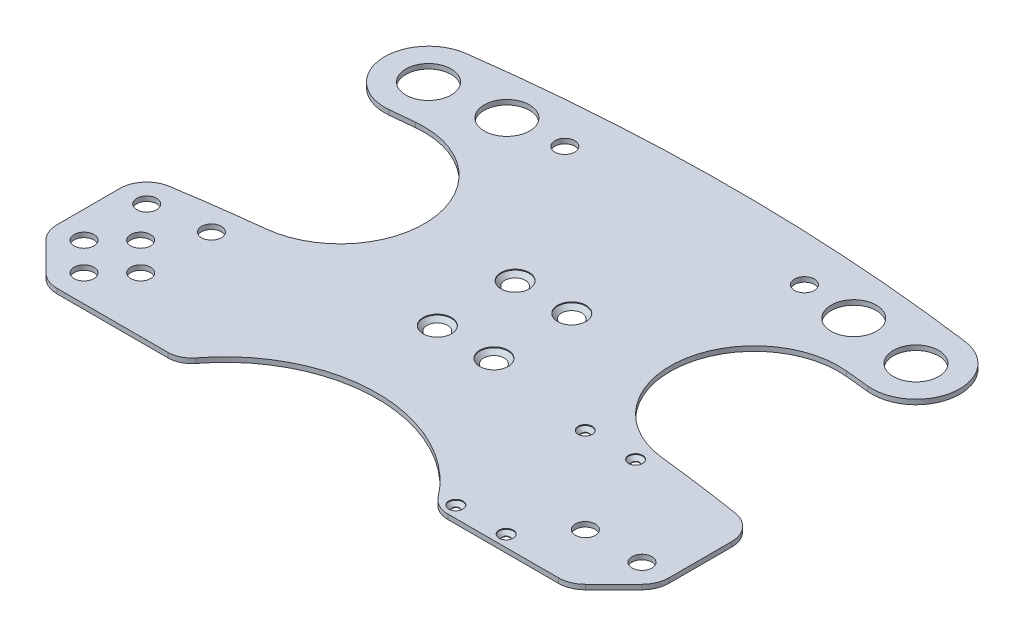
SolidWorks part; units mm, degrees
ref_plane "Front Plane" through (0, 0, 0) normal (0, 0, 1) x (1, 0, 0)
ref_plane "Top Plane" through (0, 0, 0) normal (0, 1, 0) x (1, 0, 0)
ref_plane "Right Plane" through (0, 0, 0) normal (1, 0, 0) x (0, 0, -1)
sketch "Sketch1" plane through (0, 0, 0) normal (0, 1, 0) x (1, 0, 0)
  line L1 (-120, -95) -> (120, -95)
  line L2 (-120, -95) -> (-120, 95)
  line L3 (-120, 95) -> (120, 95)
  line L4 (120, -95) -> (120, 95)
  line L5 (-120, -95) -> (120, 95) construction
  line L6 (-120, 95) -> (120, -95) construction
  line L7 (-10, 13.75) -> (10, 13.75)
  line L8 (-10, 13.75) -> (-10, -13.75)
  line L9 (-10, -13.75) -> (10, -13.75)
  line L10 (10, 13.75) -> (10, -13.75)
  line L11 (-10, 13.75) -> (10, -13.75) construction
  line L12 (-10, -13.75) -> (10, 13.75) construction
  circle A0 centre (0, 0) radius 95
  circle A1 centre (-10, 13.75) radius 2.5
  circle A2 centre (10, 13.75) radius 2.5
  circle A3 centre (10, -13.75) radius 2.5
  circle A4 centre (-10, -13.75) radius 2.5
  circle A5 centre (0, 0) radius 120
  dimension "D3" = 5
  dimension "D1" = 240
  dimension "D2" = 190
  dimension "D4" = 27.5
  dimension "D5" = 20
extrude "Boss-Extrude1" add sketch "Sketch1" along normal blind 1.7 contours A0 A4 L8 A1 L7 A2 L10 A3 L9 | A4 L9 A3 L10 A2 L7 A1 L8 | L3 A5 L1 A0 | L1 A5 L3 A0 region at (-105.6812, 0, 51.9346) region at (68.7642, 0, 68.7642) region at (-92.313, 0, 0) region at (0, 0, 0)
sketch "Sketch2" plane through (0, 1.7, 0) normal (0, 1, 0) x (1, 0, 0)
  line L0 (-81.1673, -40) -> (21.9115, -40) construction
  line L1 (-127.3056, -60) -> (138.909, -60) construction
  line L2 (-88.5406, 28.139) -> (-88.5406, -89.0376) construction
  line L3 (-88.5406, -40) -> (-88.5406, -60) construction
  line L4 (0, 21.6044) -> (0, -21.4213) construction
  line L5 (88.5406, 33.139) -> (88.5406, -84.0376) construction
  line L6 (-151.9803, -25) -> (55.006, -25) construction
  line L7 (-48.8837, 35) -> (62.426, 35) construction
  circle A0 centre (0, 0) radius 35
  circle A1 centre (0, 35) radius 2.5
  circle A2 centre (30.3109, 17.5) radius 2.5
  circle A3 centre (30.3109, -17.5) radius 2.5
  circle A4 centre (0, -35) radius 2.5
  circle A5 centre (-30.3109, -17.5) radius 2.5
  circle A6 centre (-30.3109, 17.5) radius 2.5
  circle A7 centre (-88.5406, -40) radius 3.5
  circle A8 centre (-88.5406, -50) radius 10
  circle A9 centre (-78.5406, -50) radius 3.5
  circle A10 centre (-88.5406, -60) radius 3.5
  circle A11 centre (-98.5406, -50) radius 3.5
  circle A12 centre (78.5406, -50) radius 3.5
  circle A13 centre (98.5406, -50) radius 3.5
  circle A14 centre (-98.5406, -27.8625) radius 3.5
  circle A15 centre (-78.5406, -25) radius 3.5
  circle A16 centre (0, 0) radius 45
  circle A17 centre (0, -580) radius 625
  circle A18 centre (0, -580) radius 645
  circle A19 centre (-86.0945, 59.2282) radius 8
  circle A20 centre (-61.2596, 62.0843) radius 8
  circle A21 centre (-86.0945, 59.2282) radius 15.5
  arc A22 (-73.3144, 95) -> (-73.3144, -95) centre (0, 0) ccw construction
  circle A23 centre (-61.2596, 62.0843) radius 9.5
  circle A24 centre (-86.0945, 59.2282) radius 9.5
  circle A25 centre (61.2596, 62.0843) radius 8
  circle A26 centre (86.0945, 59.2282) radius 8
  circle A27 centre (-42.3209, 63.6101) radius 3.5
  circle A28 centre (0, 0) radius 70
  circle A29 centre (42.3209, 63.6101) radius 3.5
  circle A30 centre (-98.5406, -50) radius 9.5
  circle A31 centre (42.3209, 63.6101) radius 9.5
  circle A32 centre (61.2596, 62.0843) radius 9.5
  circle A33 centre (0, -645.0455) radius 625
  point P17 (0, 0)
  point P21 (-88.5406, -50)
  point P37 (-88.5406, -50)
  point P56 (0, 65)
  point P57 (0, 45)
  point P68 (-76.6704, 60.4269)
  point P69 (-70.7097, 61.1124)
  dimension "D1" = 70
  dimension "D2" = 5
  dimension "D4" = 7
  dimension "D9" = 90
  dimension "D10" = 1250
  dimension "D11" = 20
  dimension "D12" = 16
  dimension "D14" = 6
  dimension "D13" = 19
  dimension "D17" = 140
  dimension "D18" = 6
  dimension "D5" = 20
  dimension "D6" = 40
  dimension "D8" = 15
  dimension "D15" = 6
  dimension "D3" = 6
  dimension "D7" = 4
extrude "Cut-Extrude1" cut sketch "Sketch2" against normal up to next contours A7 | A9 | A10 | A11 | A12 | A13 | A14 | A15 | A19 | A20 | A25 | A26 | A27 | A29
sketch "Sketch3" plane through (0, 1.7, 0) normal (0, 1, 0) x (1, 0, 0)
  line L1 (-84.5506, 43.8053) -> (-40.7771, 48.1872)
  line L2 (0, 100.6986) -> (0, -98.8678) construction
  line L3 (-10.3445, 0) -> (20.4144, 0) construction
  line L5 (84.5506, 43.8053) -> (40.7771, 48.1872)
  line L6 (-42.3209, 63.6101) -> (0, 0) construction
  line L7 (-36.306, 26.5871) -> (-55.2257, 55.0243)
  line L8 (-10.4964, 43.7587) -> (-29.4161, 72.1959)
  line L9 (10.4964, 43.7587) -> (29.4161, 72.1959)
  line L10 (36.306, 26.5871) -> (55.2257, 55.0243)
  line L11 (-108.0406, -50) -> (-108.0406, -27.8625)
  line L13 (-73.3144, -95) -> (73.3144, -95)
  line L14 (73.3144, 95) -> (-73.3144, 95)
  line L15 (-73.3144, -95) -> (73.3144, -95)
  line L16 (73.3144, 95) -> (-73.3144, 95)
  line L17 (-69.0406, -25) -> (-69.0406, -50)
  line L18 (-71.8231, -56.7175) -> (-81.8231, -66.7175)
  line L19 (-105.2581, -56.7175) -> (-95.2581, -66.7175)
  line L20 (-42.3209, 79.1101) -> (42.3209, 79.1101)
  line L21 (-78.5406, -15.5) -> (-42.2463, -15.5)
  line L22 (0, -45) -> (111.243, -45) construction
  line L23 (-88.5406, -69.5) -> (88.5406, -69.5)
  line L24 (69.0406, -15.5) -> (45.0406, -15.5)
  line L25 (78.5406, -15.5) -> (42.2463, -15.5)
  line L27 (108.0406, -50) -> (108.0406, -27.8625)
  line L28 (105.2581, -56.7175) -> (95.2581, -66.7175)
  line L29 (69.0406, -15.5) -> (69.0406, -69.5)
  line L30 (69.0406, -69.5) -> (45.0406, -69.5)
  line L31 (45.0406, -15.5) -> (45.0406, -69.5)
  line L32 (57.0406, -15.5) -> (57.0406, -69.5) construction
  line L33 (45.0406, -42.5) -> (69.0406, -42.5) construction
  circle A0 centre (-86.0945, 59.2282) radius 15.5
  arc A1 (-73.3144, 95) -> (-73.3144, -95) centre (0, 0) ccw construction
  circle A2 centre (-42.3209, 63.6101) radius 15.5
  circle A3 centre (86.0945, 59.2282) radius 15.5
  circle A4 centre (42.3209, 63.6101) radius 15.5
  circle A5 centre (0, 0) radius 45
  circle A6 centre (-98.5406, -27.8625) radius 9.5
  circle A7 centre (-98.5406, -27.8625) radius 3.5 construction
  arc A8 (-73.3144, 95) -> (-73.3144, -95) centre (0, 0) ccw
  arc A9 (73.3144, -95) -> (73.3144, 95) centre (0, 0) ccw
  arc A10 (-73.3144, 95) -> (-73.3144, -95) centre (0, 0) ccw
  arc A11 (73.3144, -95) -> (73.3144, 95) centre (0, 0) ccw
  circle A12 centre (-78.5406, -25) radius 9.5
  circle A13 centre (-88.5406, -60) radius 9.5
  circle A14 centre (-98.5406, -50) radius 9.5
  circle A15 centre (-78.5406, -50) radius 9.5
  circle A17 centre (98.5406, -50) radius 9.5
  circle A18 centre (78.5406, -50) radius 9.5
  arc A19 (73.3144, -95) -> (73.3144, 95) centre (0, 0) ccw construction
  arc A20 (-45.0406, -69.5) -> (45.0406, -69.5) centre (0, -98.6511) cw
  circle A21 centre (98.5406, -27.8625) radius 9.5
  circle A22 centre (98.5406, -50) radius 9.5
  circle A23 centre (88.5406, -60) radius 9.5
  circle A24 centre (-73.1485, 15.1063) radius 29.692
  circle A25 centre (73.1485, 15.1063) radius 29.692
  circle A26 centre (48.1506, -19.64) radius 1.3
  circle A27 centre (65.9306, -19.64) radius 1.3
  circle A28 centre (65.9306, -65.36) radius 1.3
  circle A29 centre (48.1506, -65.36) radius 1.3
  circle A30 centre (0, -580) radius 645
  circle A31 centre (0, -580) radius 660.5
  circle A32 centre (0, -645.0455) radius 634.5
  arc M45 (-73.3144, 95) -> (-73.3144, -95) centre (0, 0) ccw
  line M46 (-73.3144, -95) -> (73.3144, -95)
  arc M47 (73.3144, -95) -> (73.3144, 95) centre (0, 0) ccw
  line M48 (73.3144, 95) -> (-73.3144, 95)
  dimension "D1" = 90
  dimension "D3" = 6
  dimension "D5" = 2.6
  dimension "D4" = 24
  dimension "D6" = 17.78
  dimension "D7" = 45.72
  dimension "D2" = 0
extrude "Cut-Extrude2" cut sketch "Sketch3" against normal up to next contours A24 L1 A0 A14 L11 A6 L21 M45 | A24 | L28 A23 L23 A13 L19 A14 A10 A17 M46 M47 | A20 L23 | L5 A25 L24 L25 A21 L27 A17 A11 A3 | A25 | A30 A0 M45 | A31 A11 M48 M45 | A0 A31 A10 | A31 A3 M47 | A30 A3 M47 | A6 A32 A14 L11 M45 | A11 A32 A21 L27 A17 | A26 | A27 | A28 | A29 region at (-105.8887, 1.7, -12.959) region at (-73.1485, 1.7, -15.1063) region at (-102.839, 1.7, -59.5932) region at (-94.2652, 1.7, -72.7135) region at (0, 1.7, -86.2332) region at (-111.2756, 1.7, 31.2797) region at (0, 1.7, 81.3426) region at (0, 1.7, 59.4787) region at (73.1485, 1.7, -15.1063) region at (105.8887, 1.7, -12.959) region at (111.2756, 1.7, 31.2797) region at (94.2652, 1.7, -72.7135) region at (102.839, 1.7, -59.5932)
hole_wizard "CSK for M5 Flat Head Machine Screw1" positions "Sketch4" profile "Sketch5" countersink size "M5" standard "ANSI Metric"
sketch "Sketch4" plane through (0, 1.7, 0) normal (0, 1, 0) x (1, 0, 0)
  point P0 (-10, 13.75)
  point P3 (10, 13.75)
  point P6 (10, -13.75)
  point P9 (-10, -13.75)
sketch "Sketch5" plane through (-10, 1.7, -13.75) normal (1, 0, 0) x (0, 0, 1)
  line L0 (0, 0) -> (0, 6.5022)
  line L1 (0, 6.5022) -> (2.5, 5)
  line L2 (2.5, 5) -> (2.5, 2.8)
  line L3 (2.5, 2.8) -> (5, 0.3)
  line L4 (5, 0.3) -> (5, 0)
  line L6 (5, 0) -> (0, 0)
  line L7 (-2.5, 2.8) -> (-5, 0.3) construction
  line L10 (0, 6.5022) -> (-2.5, 5) construction
  line L11 (0, -6.35) -> (0, 107.95) construction
  dimension "Hole Dia." = 5
  dimension "Hole Depth" = 5
  dimension "C'Sink Dia." = 10
  dimension "C'Sink Angle" = 90
  dimension "Drill Angle" = 118
  dimension "Head Clearance" = 0.3
hole_wizard "CSK for M2.5 Flat Head Machine Screw1" positions "Sketch6" profile "Sketch7" countersink size "M2.5" standard "ANSI Metric"
sketch "Sketch6" plane through (0, 1.7, 0) normal (0, 1, 0) x (1, 0, 0)
  point P0 (48.1506, -19.64)
  point P3 (65.9306, -19.64)
  point P6 (65.9306, -65.36)
  point P9 (48.1506, -65.36)
sketch "Sketch7" plane through (48.1506, 1.7, 19.64) normal (1, 0, 0) x (0, 0, 1)
  line L0 (0, 0) -> (0, 5.7511)
  line L1 (0, 5.7511) -> (1.25, 5)
  line L2 (1.25, 5) -> (1.25, 1.55)
  line L3 (1.25, 1.55) -> (2.5, 0.3)
  line L4 (2.5, 0.3) -> (2.5, 0)
  line L6 (2.5, 0) -> (0, 0)
  line L7 (-1.25, 1.55) -> (-2.5, 0.3) construction
  line L10 (0, 5.7511) -> (-1.25, 5) construction
  line L11 (0, -6.35) -> (0, 107.95) construction
  dimension "Hole Dia." = 2.5
  dimension "Hole Depth" = 5
  dimension "C'Sink Dia." = 5
  dimension "C'Sink Angle" = 90
  dimension "Drill Angle" = 118
  dimension "Head Clearance" = 0.3
fillet "Fillet1" radius 8.5 2 edges at (45.0406, 0.85, 69.5) (-45.0406, 0.85, 69.5)
